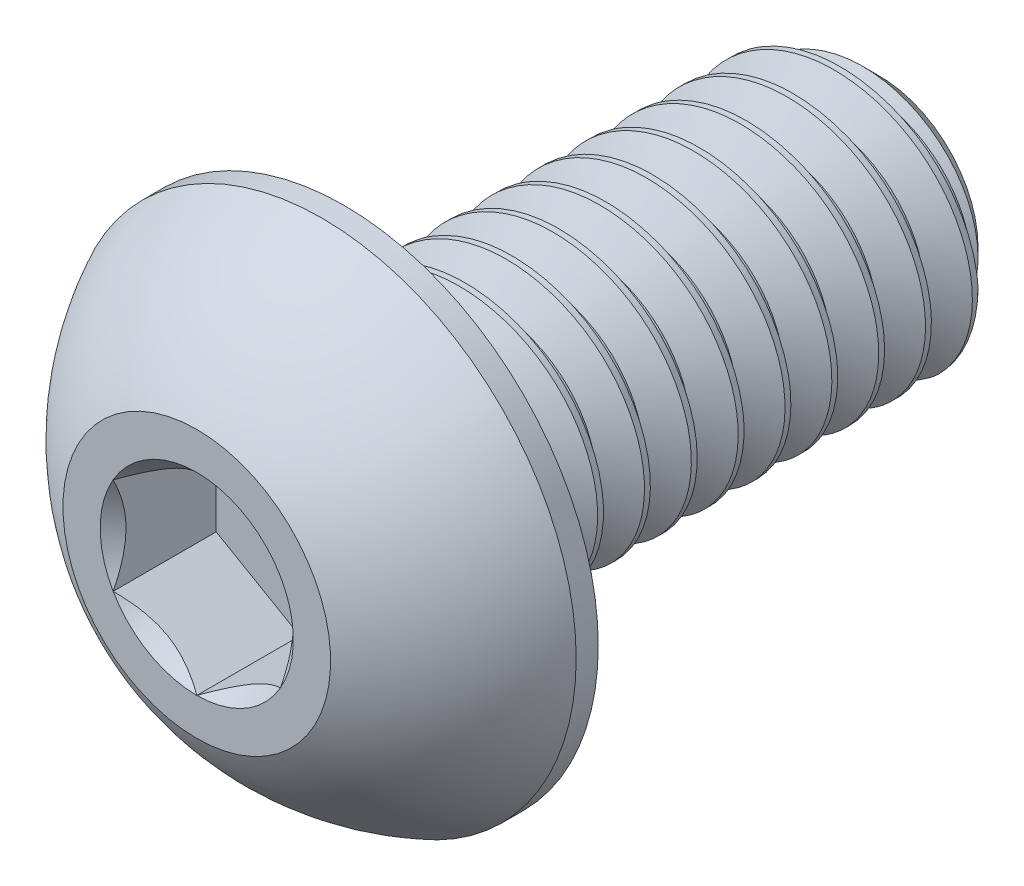
SolidWorks part; units mm, degrees
ref_plane "Front" through (0, 0, 0) normal (0, 0, 1) x (1, 0, 0)
ref_plane "Top" through (0, 0, 0) normal (0, 1, 0) x (1, 0, 0)
ref_plane "Right" through (0, 0, 0) normal (1, 0, 0) x (0, 0, -1)
sketch "Sketch1" plane through (0, 0, 0) normal (1, 0, 0) x (0, 0, -1)
  line L2 (2.2, 2) -> (10.2, 2)
  line L3 (10.2, 2) -> (10.2, 0)
  line L4 (10.2, 0) -> (2.2, 0)
  line L6 (1.87, 3.8) -> (2.2, 3.8) construction
  line L7 (10.2, 2) -> (10.2, -2) construction
  line L8 (0, 0) -> (2.2, 0) construction
  line L9 (2.2, 3.8) -> (2.2, -3.8) construction
  line L11 (2.2, 2) -> (2.2, 0)
  line L13 (0, 1.25) -> (0, -1.25) construction
  line L14 (0, 1.25) -> (0, 2) construction
  line L15 (10.1562, 2.0758) -> (10.5062, 1.4696) construction
  line L16 (10.5062, 1.4696) -> (10.8562, 2.0758) construction
  line L17 (10.8562, 2.0758) -> (10.1562, 2.0758) construction
  line L18 (10.2, 2) -> (10.8125, 2) construction
  line L19 (10.5062, 2.0758) -> (10.5062, 2) construction
  line L20 (10.5062, 2) -> (10.5062, 1.5453) construction
  line L21 (10.5062, 1.5453) -> (10.5062, 1.4696) construction
  line L22 (10.4625, 1.5453) -> (10.55, 1.5453)
  line L23 (10.1781, 2.0379) -> (10.8344, 2.0379)
  line L24 (10.55, 1.5453) -> (10.8344, 2.0379)
  line L25 (10.4625, 1.5453) -> (10.1781, 2.0379)
  line L26 (9.675, 2) -> (10.2, 1.475)
  arc A3 (0, 2) -> (1.87, 3.8) centre (3.7264, 0) cw construction
  point P29 (10.5062, 2.0379)
  point P30 (8.45, -2)
  dimension "D1" = 0.33
  dimension "Pitch" = 0.7
  dimension "D3" = 0.0875
  dimension "D2" = 0.525
  dimension "D4" = 45
  dimension "D5" = 1.75
sketch "Sketch10" plane through (0, 0, 0) normal (1, 0, 0) x (0, 0, -1)
  line L0 (9.675, 2) -> (10.2, 1.475) construction
  line L1 (9.675, 2) -> (10.2, 1.475)
  line L4 (10.2, 2) -> (2.2, 2)
  line L5 (10.2, 0) -> (10.2, 2)
  line L6 (2.2, 0) -> (10.2, 0)
  line L7 (2.2, 2) -> (2.2, 0)
  line L8 (9.675, 2) -> (2.2, 2)
  line L9 (10.2, 0) -> (10.2, 1.475)
  line L10 (2.2, 0) -> (10.2, 0)
  line L11 (2.2, 2) -> (2.2, 0)
  dimension "D1" = 0
revolve "Revolve3" add sketch "Sketch10" angle 360 about L8
sketch "Sketch7" plane through (0, 0, 0) normal (1, 0, 0) x (0, 0, -1)
  line L6 (1.87, 3.8) -> (2.2, 3.8) construction
  line L8 (0, 0) -> (2.2, 0) construction
  line L11 (2.2, 3.8) -> (2.2, -3.8) construction
  line L12 (1.87, 3.8) -> (2.2, 3.8)
  line L13 (0, 0) -> (2.2, 0)
  line L14 (0, 1.25) -> (0, -1.25) construction
  line L15 (2.2, 3.8) -> (2.2, 0)
  line L16 (0, 2) -> (0, 0)
  arc A2 (1.87, 3.8) -> (0, 2) centre (3.7264, 0) ccw construction
  arc A3 (1.87, 3.8) -> (0, 2) centre (3.7264, 0) ccw
revolve "Revolve2" add sketch "Sketch7" angle 360 mid plane about L13
sketch "Sketch5" plane through (0, 0, 0) normal (0, 0, 1) x (1, 0, 0)
  line L1 (1.25, -0.7217) -> (1.25, 0.7217)
  line L2 (1.25, 0.7217) -> (0, 1.4434)
  line L3 (0, 1.4434) -> (-1.25, 0.7217)
  line L4 (-1.25, 0.7217) -> (-1.25, -0.7217)
  line L5 (-1.25, -0.7217) -> (0, -1.4434)
  line L6 (0, -1.4434) -> (1.25, -0.7217)
  circle A0 centre (0, 0) radius 1.25 construction
extrude "Cut-Extrude2" cut sketch "Sketch5" against normal blind 1.54
sketch "Sketch6" plane through (0, 0, 0) normal (0, 0, 1) x (1, 0, 0)
  circle A0 centre (0, 0) radius 1.4434
extrude "Cut-Extrude3" cut sketch "Sketch6" against normal blind 1.54 draft 45
sketch "Sketch9" plane through (0, 0, -2.2) normal (0, 0, -1) x (-1, 0, 0)
  circle A0 centre (0, 0) radius 2 construction
  circle A4 centre (0, 0) radius 2
split "Split1" bodies to split 113 resulting bodies 123 124 split by face at (3.8, 0, -2.2)
sketch "Sketch11" plane through (0, 0, -10.2) normal (0, 0, -1) x (-1, 0, 0)
  circle A0 centre (0, 0) radius 2 construction
  circle A1 centre (0, 0) radius 2
curve "Helix/Spiral1" pitch 0.7 height 10.2 radius 2 centre (0, 0, -10.2) axis (0, 0, 1) start towards (0, 1, 0)
sketch "Sketch12" plane through (0, 0, 0) normal (1, 0, 0) x (0, 0, -1)
  line L0 (10.4625, 1.5453) -> (10.55, 1.5453) construction
  line L1 (10.55, 1.5453) -> (10.8344, 2.0379) construction
  line L2 (10.1781, 2.0379) -> (10.8344, 2.0379) construction
  line L3 (10.4625, 1.5453) -> (10.1781, 2.0379) construction
  line L4 (10.4625, 1.5453) -> (10.55, 1.5453)
  line L5 (10.55, 1.5453) -> (10.8344, 2.0379)
  line L6 (10.1781, 2.0379) -> (10.8344, 2.0379)
  line L7 (10.4625, 1.5453) -> (10.1781, 2.0379)
sweep "Cut-Sweep2" cut profiles "Sketch12" path "Helix/Spiral1" align with end faces yes
extrude "Boss-Extrude1" add sketch "Sketch9" along normal blind 10 draft 45
equation "\"D1@Cut-Extrude2\" = \"Head Ht@Sketch1\" * .7"
equation "\"D1@Sketch1\" = \"Head Ht@Sketch1\" * .15"
equation "\"D1@Cut-Extrude3\" = \"D1@Cut-Extrude2\""
equation "\"D3@Sketch1\" = \"Pitch@Sketch1\" / 8"
equation "\"D2@Sketch1\"=\"Pitch@Sketch1\"*0.75"
equation "\"D3@Helix/Spiral1\" = \"Lg@Sketch1\" + \"Head Ht@Sketch1\""
equation "\"D4@Helix/Spiral1\"=\"pitch@sketch1\""
equation "\"D5@Sketch1\"=\"Pitch@Sketch1\"*2.5"
